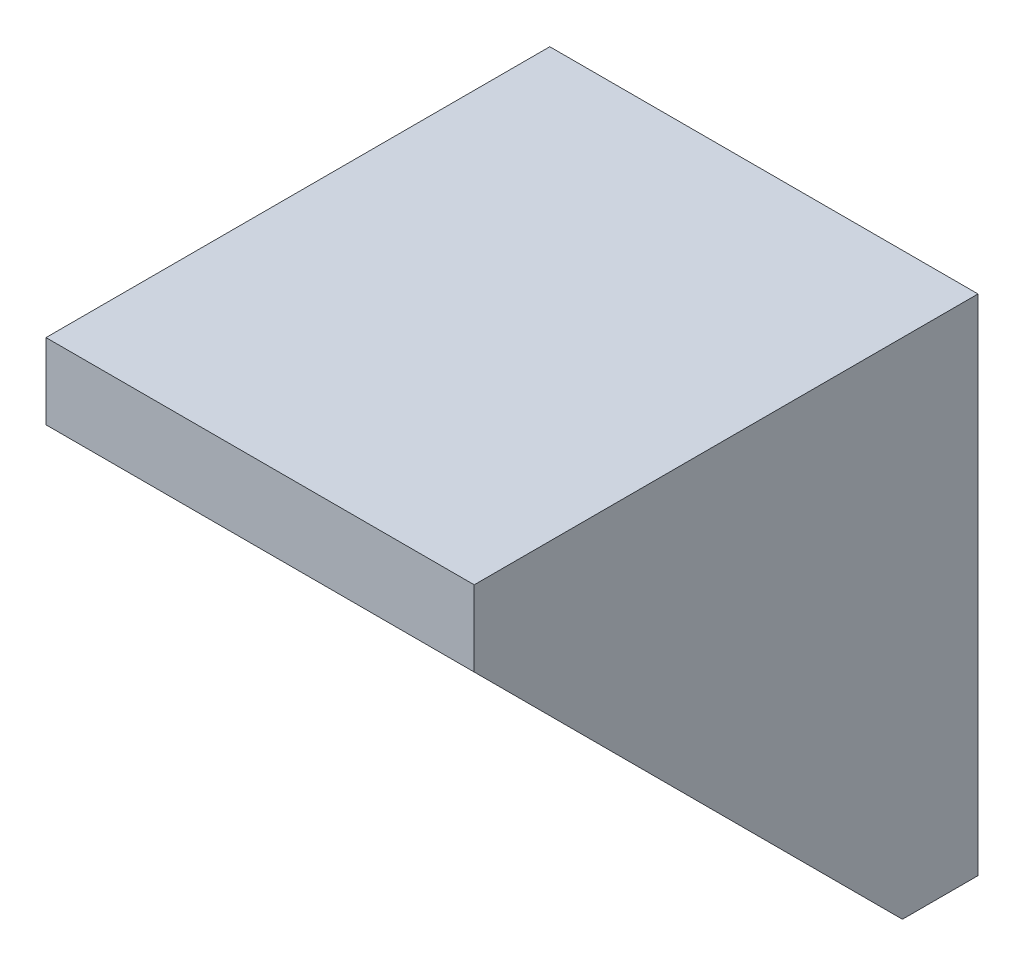
SolidWorks part; units mm, degrees
material "1060 Alloy"
ref_plane "Front Plane" through (0, 0, 0) normal (0, 0, 1) x (1, 0, 0)
ref_plane "Top Plane" through (0, 0, 0) normal (0, 1, 0) x (1, 0, 0)
ref_plane "Right Plane" through (0, 0, 0) normal (1, 0, 0) x (0, 0, -1)
sketch "Sketch1" plane through (0, 0, 0) normal (1, 0, 0) x (0, 0, -1)
  line L0 (0, 0) -> (-20, 0)
  line L1 (-20, 0) -> (-20, -3)
  line L2 (-20, -3) -> (-11.5, -11.5)
  line L3 (-11.5, -11.5) -> (0, 0) construction
  line L4 (-3, -20) -> (-11.5, -11.5)
  line L5 (0, -20) -> (-3, -20)
  line L6 (0, 0) -> (0, -20)
  dimension "D1" = 3
  dimension "D2" = 20
extrude "Boss-Extrude1" add sketch "Sketch1" along normal mid plane 17
sketch "Sketch2" plane through (0, 0, 0) normal (1, 0, 0) x (0, 0, -1)
  line L0 (-20, -3) -> (-3, -20) construction
  line L1 (-3, -3) -> (-20, -3)
  line L2 (-3, -3) -> (-3, -20)
  line L3 (-3, -20) -> (-20, -20)
  line L4 (-20, -3) -> (-20, -20)
  line L5 (-20, 0) -> (-20, -3) construction
extrude "Cut-Extrude1" cut sketch "Sketch2" against normal mid plane 12
sketch "Sketch3" plane through (0, 0, 3) normal (0, 0, 1) x (1, 0, 0)
  line L0 (0, -9) -> (0, -12) construction
  line L1 (-3, -9) -> (-3, -12)
  line L2 (3, -9) -> (3, -12)
  line L3 (0, -10.5) -> (0.7454, -10.5) construction
  line L4 (-6, -20) -> (6, -20) construction
  arc A0 (-3, -9) -> (3, -9) centre (0, -9) cw
  arc A1 (-3, -12) -> (3, -12) centre (0, -12) ccw
  dimension "D3" = 9
  dimension "D4" = 5
  dimension "D1" = 3
  dimension "D2" = 3
extrude "Cut-Extrude2" cut sketch "Sketch3" against normal up to next
